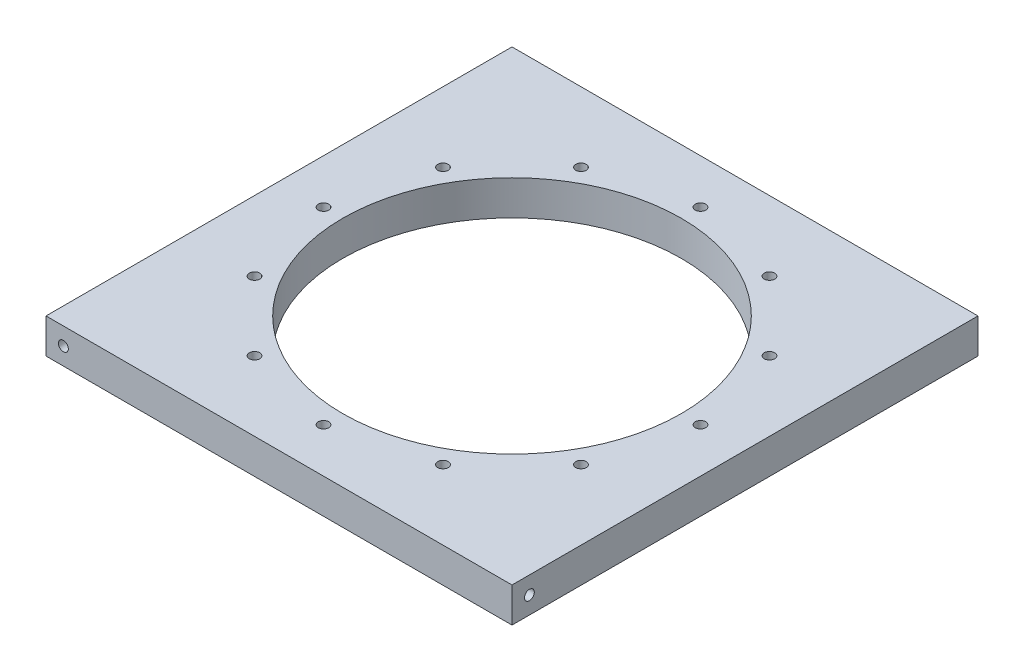
SolidWorks part; units mm, degrees
material "6061-T6 (SS)"
ref_plane "Front Plane" through (0, 0, 0) normal (0, 0, 1) x (1, 0, 0)
ref_plane "Top Plane" through (0, 0, 0) normal (0, 1, 0) x (1, 0, 0)
ref_plane "Right Plane" through (0, 0, 0) normal (1, 0, 0) x (0, 0, -1)
sketch "Sketch1" plane through (0, 0, 0) normal (0, 1, 0) x (1, 0, 0)
  line L5 (0, 0) -> (127.635, 0)
  line L6 (0, 0) -> (0, 127.635)
  line L7 (0, 127.635) -> (127.635, 127.635)
  line L8 (127.635, 0) -> (127.635, 127.635)
  dimension "D1" = 127.635
  dimension "D2" = 127.635
extrude "Boss-Extrude1" add sketch "Sketch1" along normal blind 9.525 contours L5 L8 L7 L6
sketch "Sketch5" plane through (0, 9.525, 0) normal (0, 1, 0) x (1, 0, 0)
  line L0 (63.8175, 0) -> (63.8175, 127.635) construction
  line L3 (0, 0) -> (127.635, 0) construction
  line L8 (0, 127.635) -> (127.635, 127.635) construction
  circle A0 centre (63.8175, 63.8175) radius 46.355
  dimension "D1" = 92.71
extrude "Cut-Extrude1" cut sketch "Sketch5" against normal blind 9.525 contours L0 A0 | A0 L0
sketch "Sketch11" plane through (0, 9.525, 0) normal (0, 1, 0) x (1, 0, 0)
  line L0 (63.8175, 63.8175) -> (63.8175, 115.443) construction
  circle A0 centre (63.8175, 115.443) radius 1.4351
  dimension "D2" = 2.8702
  dimension "D1" = 51.6255
extrude "Cut-Extrude3" cut sketch "Sketch11" against normal through all contours A0
pattern_circular "CirPattern1" count 12 over 360 about axis through (63.8175, 9.525, -63.8175) along (0, 1, 0) of "Cut-Extrude3"
sketch "Sketch6" plane through (127.635, 0, 0) normal (1, 0, 0) x (0, 0, -1)
  circle A0 centre (4.7625, 4.7625) radius 1.3526
  dimension "D1" = 2.7051
extrude "6-32 hole1" cut sketch "Sketch6" against normal blind 12.7
sketch "Sketch7" plane through (0, 0, -127.635) normal (0, 0, -1) x (-1, 0, 0)
  circle A0 centre (-122.8725, 4.7625) radius 1.3525
  dimension "D1" = 2.7051
sketch "Sketch8" plane through (0, 0, 0) normal (-1, 0, 0) x (0, 0, 1)
  circle A0 centre (-122.8725, 4.7625) radius 1.3525
  dimension "D1" = 2.7051
sketch "Sketch9" plane through (0, 0, 0) normal (0, 0, 1) x (1, 0, 0)
  circle A0 centre (4.7625, 4.7625) radius 1.3526
  dimension "D1" = 2.7051
extrude "6-32 hole2" cut sketch "Sketch7" against normal blind 12.7
extrude "6-32 hole3" cut sketch "Sketch8" against normal blind 12.7
extrude "6-32 hole4" cut sketch "Sketch9" against normal blind 12.7
